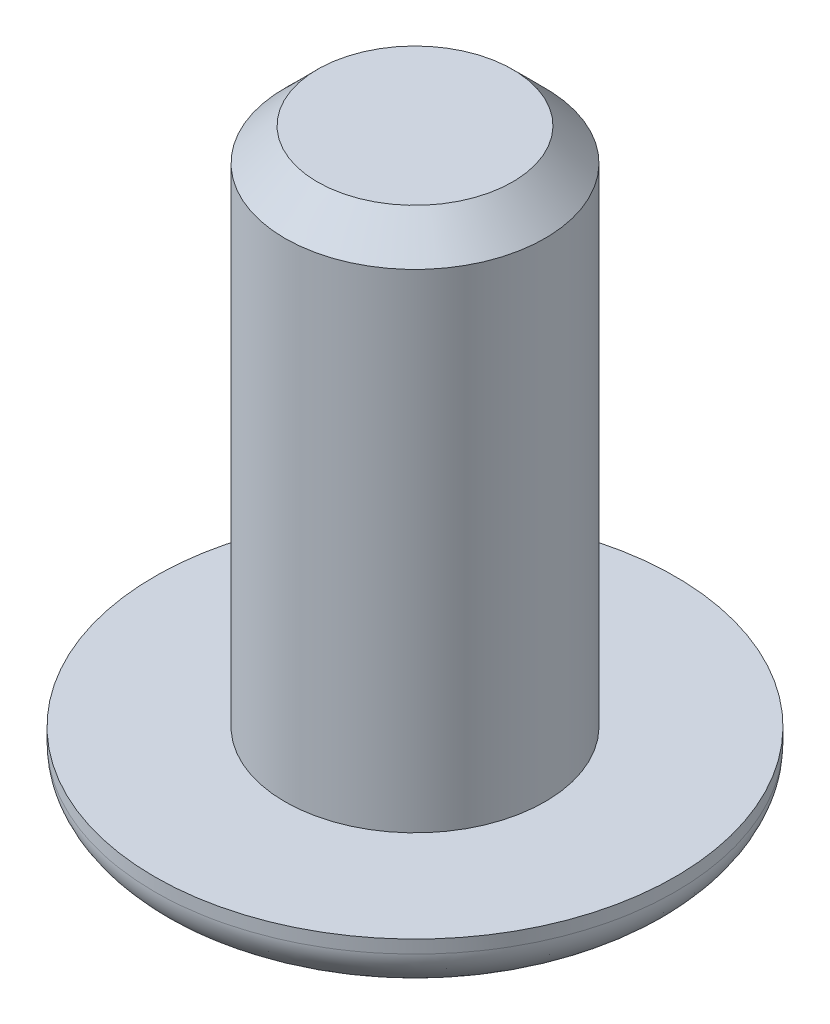
SolidWorks part; units mm, degrees
material "ASTM A36 钢"
ref_plane "前视基准面" through (0, 0, 0) normal (0, 0, 1) x (1, 0, 0)
ref_plane "上视基准面" through (0, 0, 0) normal (0, 1, 0) x (1, 0, 0)
ref_plane "右视基准面" through (0, 0, 0) normal (1, 0, 0) x (0, 0, -1)
sketch "草图1" plane through (0, 0, 0) normal (0, 1, 0) x (1, 0, 0)
  line L1 (1.4434, 0) -> (0.7217, 1.25)
  line L2 (0.7217, 1.25) -> (-0.7217, 1.25)
  line L3 (-0.7217, 1.25) -> (-1.4434, 0)
  line L4 (-1.4434, 0) -> (-0.7217, -1.25)
  line L5 (-0.7217, -1.25) -> (0.7217, -1.25)
  line L6 (0.7217, -1.25) -> (1.4434, 0)
  circle A0 centre (0, 0) radius 4
  circle A1 centre (0, 0) radius 1.25 construction
extrude "凸台-拉伸1" add sketch "草图1" along normal blind 1.2
sketch "草图2" plane through (0, 1.2, 0) normal (0, 1, 0) x (1, 0, 0)
  circle A0 centre (0, 0) radius 2
extrude "凸台-拉伸2" add sketch "草图2" along normal blind 8
chamfer "倒角1" distance 0.5 angle 45 1 edges at (0, 9.2, 2)
fillet "圆角1" radius 2 1 edges at (0, 0, 4) second distance 1 first distance on face at (0, 0, 4)
